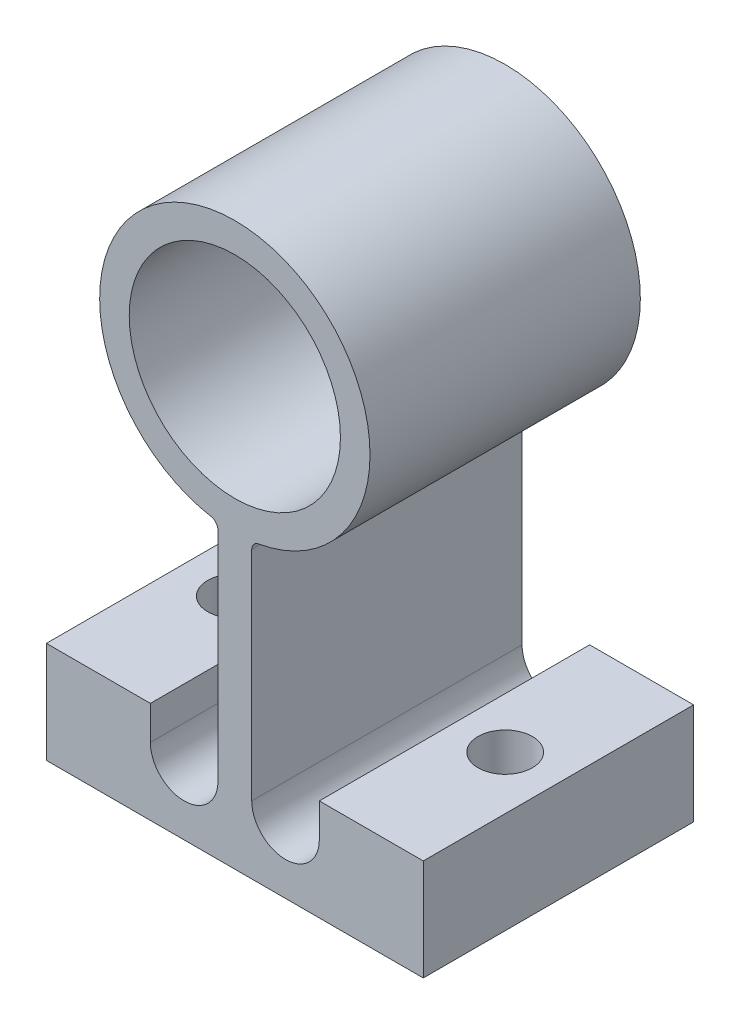
SolidWorks part; units mm, degrees
material "6061 Alloy"
ref_plane "Front Plane" through (0, 0, 0) normal (0, 0, 1) x (1, 0, 0)
ref_plane "Top Plane" through (0, 0, 0) normal (0, 1, 0) x (1, 0, 0)
ref_plane "Right Plane" through (0, 0, 0) normal (1, 0, 0) x (0, 0, -1)
sketch "Sketch1" plane through (0, 0, 0) normal (0, 0, -1) x (1, 0, 0)
  line L0 (0, 0) -> (0, 40.0837) construction
  line L1 (-17.706, 40.0837) -> (17.706, 40.0837)
  line L2 (17.706, 40.0837) -> (17.706, 30.5587)
  line L3 (17.706, 30.5587) -> (1.5875, 30.5587)
  line L4 (1.5875, 12.6004) -> (1.5875, 30.5587)
  line L5 (-1.5875, 12.6004) -> (-1.5875, 30.5587)
  line L6 (-17.706, 30.5587) -> (-1.5875, 30.5587)
  line L7 (-17.706, 40.0837) -> (-17.706, 30.5587)
  arc A0 (-1.5875, 12.6004) -> (1.5875, 12.6004) centre (0, 0) ccw
  circle A1 centre (0, 0) radius 9.9219
  dimension "D2" = 25.4
  dimension "D3" = 19.8438
  dimension "D1" = 40.0837
  dimension "D4" = 35.4119
  dimension "D5" = 3.175
  dimension "D6" = 9.525
extrude "Extrude1" add sketch "Sketch1" along normal mid plane 25.4
fillet "Bushing-side fillets" radius 0.7937 2 edges at (1.5875, -12.6004, 0) (-1.5875, -12.6004, 0)
fillet "Mount-side fillets" radius 0.7937 2 edges at (1.5875, -30.5587, 0) (-1.5875, -30.5587, 0)
hole_wizard "1/4 Mounting holes" positions "Sketch3" profile "Sketch2" tap size "1/4-20" standard "Ansi Inch"
sketch "Sketch3" plane through (0, -40.0837, 0) normal (0, -1, 0) x (1, 0, 0)
  line L0 (0, -12.7) -> (0, 12.7) construction
  line L1 (17.706, -12.7) -> (-17.706, -12.7) construction
  line L2 (17.706, 12.7) -> (-17.706, 12.7) construction
  point P0 (-12.7, 0)
  point P12 (12.7, 0)
  dimension "D1" = 25.4
sketch "Sketch2" plane through (-12.7, -40.0837, 0) normal (1, 0, 0) x (0, 0, -1)
  line L0 (0, 0) -> (0, 20.5838)
  line L1 (0, 20.5838) -> (2.5527, 19.05)
  line L2 (2.5527, 19.05) -> (2.5527, 0)
  line L5 (2.5527, 0) -> (0, 0)
  line L10 (0, 20.5838) -> (-2.5527, 19.05) construction
  line L11 (0, -6.35) -> (0, 107.95) construction
  dimension "Tap Drill Dia." = 5.1054
  dimension "Tap Drill Depth" = 19.05
  dimension "Drill Angle" = 118
cosmetic thread "Hole Thread1" parameters "D1"=12.7, "D2"=6.35
cosmetic thread "Hole Thread2" parameters "D1"=12.7, "D2"=6.35
sketch "Sketch4" plane through (0, 0, -12.7) normal (0, 0, -1) x (-1, 0, 0)
  line L0 (1.5875, -29.7649) -> (1.5875, -33.7337)
  line L1 (7.9375, -33.7337) -> (7.9375, -30.5587)
  line L2 (17.706, -30.5587) -> (2.3812, -30.5587) construction
  line L3 (7.9375, -30.5587) -> (2.3812, -30.5587)
  line L4 (-17.706, -40.0837) -> (17.706, -40.0837) construction
  line L5 (0, 0) -> (0, -40.0837) construction
  line L6 (-7.9375, -30.5587) -> (-2.3812, -30.5587)
  line L7 (-7.9375, -33.7337) -> (-7.9375, -30.5587)
  line L8 (-1.5875, -29.7649) -> (-1.5875, -33.7337)
  arc A0 (1.5875, -33.7337) -> (7.9375, -33.7337) centre (4.7625, -33.7337) ccw
  arc A1 (1.5875, -29.7649) -> (2.3812, -30.5587) centre (2.3812, -29.7649) ccw construction
  arc A2 (1.5875, -29.7649) -> (2.3812, -30.5587) centre (2.3812, -29.7649) ccw
  circle A3 centre (4.7625, -33.7337) radius 3.175 construction
  circle A4 centre (-4.7625, -33.7337) radius 3.175 construction
  arc A5 (-1.5875, -29.7649) -> (-2.3812, -30.5587) centre (-2.3812, -29.7649) cw
  arc A6 (-1.5875, -33.7337) -> (-7.9375, -33.7337) centre (-4.7625, -33.7337) cw
  point P11 (4.7625, -36.9087)
  point P24 (-4.7625, -36.9087)
  dimension "D1" = 6.35
  dimension "D2" = 3.175
extrude "Extrude2" cut sketch "Sketch4" against normal through all
